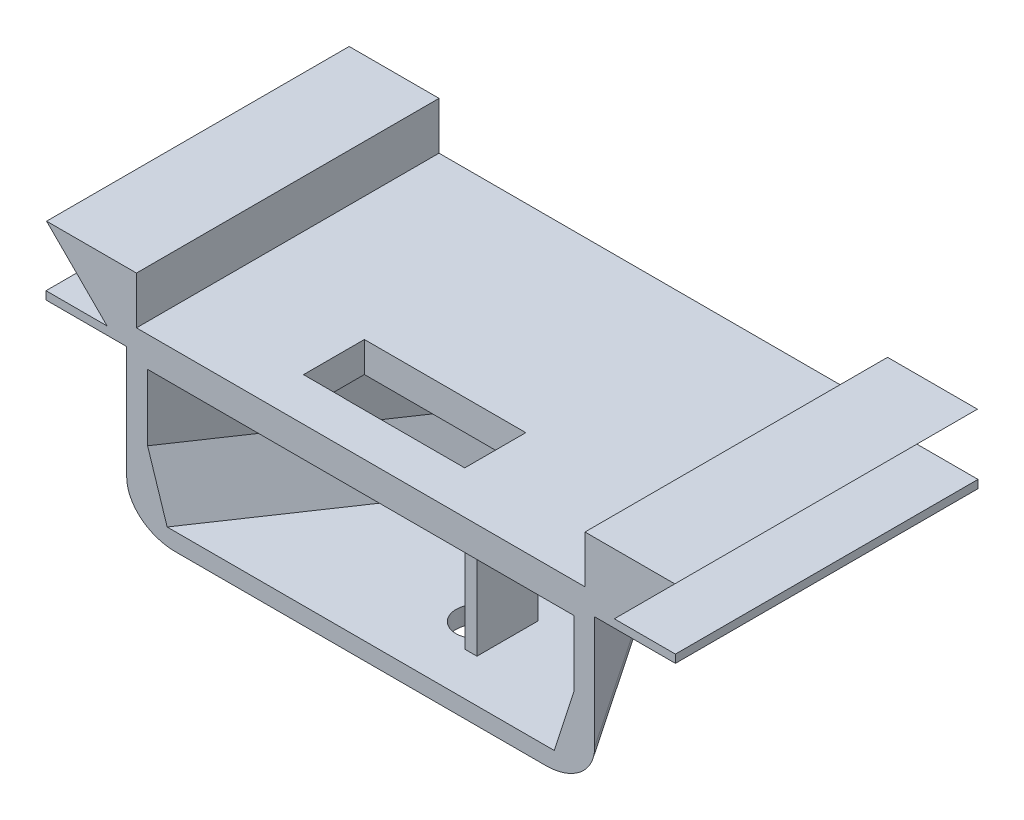
SolidWorks part; units mm, degrees
other "Camera1"
ref_plane "Front Plane" through (0, 0, 0) normal (0, 0, 1) x (1, 0, 0)
ref_plane "Top Plane" through (0, 0, 0) normal (0, 1, 0) x (1, 0, 0)
ref_plane "Right Plane" through (0, 0, 0) normal (1, 0, 0) x (0, 0, -1)
sketch "Sketch1" plane through (0, 0, 0) normal (0, 1, 0) x (1, 0, 0)
  line L0 (0, 0) -> (-116, 0)
  line L1 (-116, 0) -> (-75.5008, 60)
  line L2 (-75.5008, 60) -> (-40.5008, 60)
  line L3 (-40.5008, 60) -> (0, 0)
  dimension "D1" = 60
  dimension "D2" = 116
  dimension "D3" = 35
  dimension "D5" = 72.39
  dimension "D6" = 72.3891
extrude "Boss-Extrude1" add sketch "Sketch1" against normal blind 40
shell "Shell1" thickness 4.2918 removed face at (-58, -20, 0)
chamfer "Chamfer3" distance 15 angle 15 2 edges at (-92.0209, -35.7082, -27.8541) (-23.9799, -35.7082, -27.8541) first distance on face at (-92.0209, -20, -27.8541) first distance on face at (-23.9799, -20, -27.8541)
fillet "Fillet1" radius 10 2 edges at (-20.2504, -40, -30) (-95.7504, -40, -30)
fillet "Fillet2" radius 5 5 edges at (-40.5008, -15, -60) (-44.0345, -37.0711, -60) (-75.5008, -15, -60) (-71.9671, -37.0711, -60) (-58.0008, -40, -60)
sketch "Sketch12" plane through (0, -40, 0) normal (0, -1, 0) x (-1, 0, 0)
  circle A0 centre (47.2824, 18.1003) radius 5.2
sketch "Sketch13" plane through (0, -4.2918, 0) normal (0, -1, 0) x (1, 0, 0)
  line L1 (-39.8423, -25.7584) -> (-42.8423, -25.7584)
  line L2 (-39.8423, -25.7584) -> (-39.8423, -10.6584)
  line L3 (-39.8423, -10.6584) -> (-42.8423, -10.6584)
  line L4 (-42.8423, -25.7584) -> (-42.8423, -10.6584)
  dimension "D1" = 3
extrude "Boss-Extrude3" add sketch "Sketch13" along normal blind 35
extrude "Cut-Extrude12" cut sketch "Sketch12" against normal blind 9
sketch "Sketch15" plane through (0, 0, 0) normal (0, 1, 0) x (1, 0, 0)
  line L8 (-136, 75) -> (20, 75)
  line L9 (20, 0) -> (20, 75)
  line L10 (20, 0) -> (-136, 0)
  line L11 (-136, 0) -> (-136, 75)
extrude "Boss-Extrude7" add sketch "Sketch15" along normal blind 15
sketch "Sketch16" plane through (0, 0, 0) normal (0, 0, 1) x (1, 0, 0)
  line L1 (20.1, 15.2414) -> (20.1, -0.1)
  line L3 (20.1, -0.1) -> (4.7586, -0.1)
  line L6 (4.7586, -0.1) -> (20.1, 15.2414)
  line L8 (20, 15) -> (20, 0) construction
  line L9 (20, 0) -> (5, 0) construction
  line L10 (0, 0) -> (20, 0) construction
  line L11 (5, 0) -> (20, 15) construction
  dimension "D1" = 15
  dimension "D2" = 0.1
extrude "Cut-Extrude14" cut sketch "Sketch16" against normal blind 75
sketch "Sketch17" plane through (0, 0, 0) normal (0, 0, 1) x (1, 0, 0)
  line L0 (-136, 15) -> (-136, 0) construction
  line L1 (-136, 0) -> (-121, 0) construction
  line L2 (-136, 0) -> (-116, 0) construction
  line L3 (-121, 0) -> (-136, 15) construction
  line L4 (-120.7586, -0.1) -> (-136.1, 15.2414)
  line L5 (-136.1, 15.2414) -> (-136.1, -0.1)
  line L6 (-136.1, -0.1) -> (-120.7586, -0.1)
  dimension "D1" = 0.1
extrude "Cut-Extrude15" cut sketch "Sketch17" against normal blind 75
sketch "Sketch18" plane through (0, 0, 0) normal (0, -1, 0) x (1, 0, 0)
  line L0 (-116, 0) -> (-121, 0)
  line L1 (-121, 0) -> (-136.0045, 0)
  line L2 (-136.0045, 0) -> (-136.0045, -75)
  line L3 (-136.0045, -75) -> (-121, -75)
  line L5 (20.0045, -75) -> (20.0045, 0)
  line L6 (20.0045, 0) -> (-116, 0)
  line L7 (20.0045, -75) -> (4.5, -75)
  line L8 (-121, -75) -> (4.5, -75)
  dimension "D1" = 75
extrude "Boss-Extrude8" add sketch "Sketch18" along normal blind 2 contours L8 L7 L5 L6 L0 L1 L2 L3
sketch "Sketch20" plane through (0, -2, 0) normal (0, -1, 0) x (-1, 0, 0)
  line L1 (42.8423, 25.7218) -> (72.8207, 25.7218)
  line L2 (42.8423, 25.7218) -> (42.8423, 10.6218)
  line L3 (42.8423, 10.6218) -> (72.8207, 10.6218)
  line L4 (72.8207, 25.7218) -> (72.8207, 10.6218)
extrude "Cut-Extrude17" cut sketch "Sketch20" against normal blind 39 contours L2 L1 L4 L3
sketch "Sketch21" plane through (0, 0, 0) normal (0, 0, 1) x (1, 0, 0)
  line L6 (-135.8586, 15) -> (19.8586, 15) construction
  line L7 (-2.413, 15) -> (-113.583, 15)
  line L9 (-2.413, 15) -> (-113.583, 15)
  line L11 (-2.413, 15) -> (-2.413, 3.2309)
  line L12 (-2.413, 3.2309) -> (-113.583, 3.2309)
  line L13 (-113.583, 15) -> (-113.583, 3.2309)
extrude "Cut-Extrude18" cut sketch "Sketch21" against normal blind 80 contours L11 L9 L13 L12
sketch "Sketch22" plane through (-42.8423, 0, 0) normal (-1, 0, 0) x (0, 0, 1)
  line L1 (-10.6584, -35.7082) -> (-18.2084, -35.7082)
  line L2 (-10.6584, -35.7082) -> (-10.6584, -10.7935)
  line L3 (-10.6584, -10.7935) -> (-18.2084, -10.7935)
  line L4 (-18.2084, -35.7082) -> (-18.2084, -10.7935)
  circle A0 centre (-18.2084, -10.7935) radius 2.4
  dimension "D1" = 4.8
extrude "Cut-Extrude19" cut sketch "Sketch22" against normal blind 10 contours A0
sketch "Sketch27" plane through (0, -4.2918, 0) normal (0, -1, 0) x (-1, 0, 0)
  line L1 (42.8423, 10.6584) -> (82.8423, 10.6584)
  line L2 (42.8423, 10.6584) -> (42.8423, 25.7584)
  line L3 (42.8423, 25.7584) -> (82.8423, 25.7584)
  line L4 (82.8423, 10.6584) -> (82.8423, 25.7584)
extrude "Cut-Extrude24" cut sketch "Sketch27" against normal blind 19 contours L2 L1 L4 L3
sketch "Sketch28" plane through (0, 0, -55.7082) normal (0, 0, 1) x (1, 0, 0)
  line L1 (-53.7518, -25.9418) -> (-62.2518, -25.9418)
  line L2 (-53.7518, -25.9418) -> (-53.7518, -17.4418)
  line L3 (-53.7518, -17.4418) -> (-62.2518, -17.4418)
  line L4 (-62.2518, -25.9418) -> (-62.2518, -17.4418)
  line L10 (-42.7818, -20.7082) -> (-42.7818, -4.2918) construction
  line L12 (-42.7818, -4.2918) -> (-73.2197, -4.2918) construction
  point P4 (-23.4441, -32.4854)
  dimension "D1" = 10.97
  dimension "D2" = 13.15
sketch "Sketch30" plane through (0, 0, -55.7082) normal (0, 0, 1) x (1, 0, 0)
  line L0 (-62.2518, -25.9418) -> (-62.2518, -17.4418) construction
  line L1 (-42.7818, -4.2918) -> (-73.2197, -4.2918) construction
  circle A0 centre (-68.5018, -21.7918) radius 1.1 construction
  circle A1 centre (-68.5018, -21.7918) radius 1.35
  dimension "D1" = 6.25
  dimension "D2" = 17.5
  dimension "D3" = 0.25
sketch "Sketch31" plane through (0, 0, -55.7082) normal (0, 0, 1) x (1, 0, 0)
  line L0 (-42.7818, -4.2918) -> (-73.2197, -4.2918) construction
  line L1 (-62.2518, -25.9418) -> (-62.2518, -17.4418) construction
  circle A0 centre (-68.5018, -9.2918) radius 1.1 construction
  circle A1 centre (-68.5018, -9.2918) radius 1.35
  dimension "D1" = 5
  dimension "D2" = 6.25
  dimension "D3" = 0.25
extrude "Cut-Extrude25" cut sketch "Sketch28" against normal blind 10
extrude "Cut-Extrude26" cut sketch "Sketch30" against normal blind 10
extrude "Cut-Extrude27" cut sketch "Sketch31" against normal blind 10
sketch "Sketch32" plane through (0, 0, -55.7082) normal (0, 0, 1) x (1, 0, 0)
  line L0 (-53.7518, -25.9418) -> (-53.7518, -17.4418) construction
  line L1 (-42.7818, -4.2918) -> (-73.2197, -4.2918) construction
  circle A0 centre (-47.5018, -21.7918) radius 1.1 construction
  circle A1 centre (-47.5018, -9.2918) radius 1.1 construction
  circle A2 centre (-47.5018, -21.7918) radius 1.35
  circle A3 centre (-47.5018, -9.2918) radius 1.35
  point P8 (-44.2411, -13.5373)
  point P9 (-51.3196, -24.7658)
  dimension "D1" = 6.25
  dimension "D2" = 17.5
  dimension "D3" = 5
  dimension "D4" = 6.25
  dimension "D5" = 0.25
  dimension "D6" = 0.25
extrude "Cut-Extrude29" cut sketch "Sketch32" against normal blind 10
